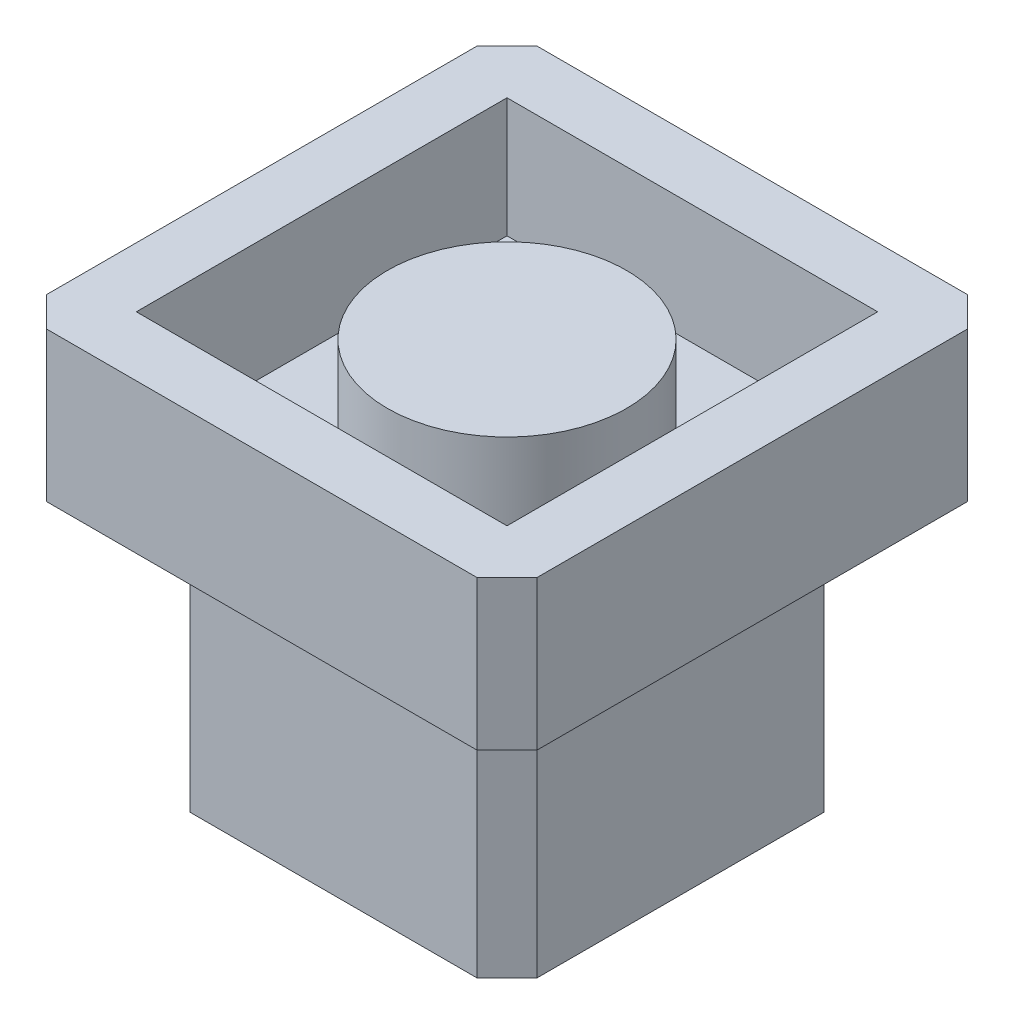
SolidWorks part; units mm, degrees
ref_plane "Front Plane" through (0, 0, 0) normal (0, 0, 1) x (1, 0, 0)
ref_plane "Top Plane" through (0, 0, 0) normal (0, 1, 0) x (1, 0, 0)
ref_plane "Right Plane" through (0, 0, 0) normal (1, 0, 0) x (0, 0, -1)
sketch "Sketch1" plane through (0, 0, 0) normal (0, 1, 0) x (1, 0, 0)
  line L0 (-4.1, 4.1) -> (-4.1, -4.1)
  line L1 (-3.1, 3.1) -> (3.1, 3.1)
  line L2 (-3.1, 3.1) -> (-3.1, -3.1)
  line L3 (-3.1, -3.1) -> (3.1, -3.1)
  line L4 (3.1, 3.1) -> (3.1, -3.1)
  line L5 (-3.1, 3.1) -> (3.1, -3.1) construction
  line L6 (-3.1, -3.1) -> (3.1, 3.1) construction
  line L7 (-4.1, -4.1) -> (4.1, -4.1)
  line L8 (4.1, 4.1) -> (4.1, -4.1)
  line L9 (-4.1, 4.1) -> (4.1, 4.1)
  circle A1 centre (0, 0) radius 2
  dimension "D1" = 4
  dimension "D2" = 6.2
  dimension "D3" = 1
extrude "Boss-Extrude1" add sketch "Sketch1" along normal blind 1.6 contours A1 region at (0, 0, 0)
extrude "Boss-Extrude2" add sketch "Sketch1<3>" along normal blind 2 separate body contours L9 L0 L7 L8 L1 L4 L3 L2 region at (0, 0, -3.984)
sketch "Sketch1<3>" plane through (0, 0, 0) normal (0, 1, 0) x (1, 0, 0) same geometry as "Sketch1"
extrude "Boss-Extrude3" add sketch "Sketch1<4>" against normal blind 0.5 contours L9 L0 L7 L8 L1 L4 L3 L2 | L4 L1 L2 L3 A1 | A1 region at (0, 0, -3.984) region at (0, 0, -3.0123) region at (0, 0, 0)
sketch "Sketch1<4>" plane through (0, 0, 0) normal (0, 1, 0) x (1, 0, 0) same geometry as "Sketch1"
sketch "Sketch3" plane through (0, -0.5, 0) normal (0, -1, 0) x (1, 0, 0)
  line L1 (-2.9, 2.9) -> (2.9, 2.9)
  line L2 (-2.9, 2.9) -> (-2.9, -2.9)
  line L3 (-2.9, -2.9) -> (2.9, -2.9)
  line L4 (2.9, 2.9) -> (2.9, -2.9)
  line L5 (-2.9, 2.9) -> (2.9, -2.9) construction
  line L6 (-2.9, -2.9) -> (2.9, 2.9) construction
  point P0 (0, 0)
  dimension "D1" = 5.8
  dimension "D2" = 5.8
extrude "Boss-Extrude4" add sketch "Sketch3" along normal blind 4.5
chamfer "Chamfer1" distance 0.5 angle 45 8 edges at (-4.1, 0.75, -4.1) (4.1, 0.75, -4.1) (-4.1, 0.75, 4.1) (4.1, 0.75, 4.1) (-2.9, -2.75, 2.9) (2.9, -2.75, 2.9) (-2.9, -2.75, -2.9) (2.9, -2.75, -2.9)
sketch "Sketch4" plane through (0, -5, 0) normal (0, -1, 0) x (1, 0, 0)
  text T1 "B\r\n"
extrude "Cut-Extrude1" cut sketch "Sketch4" against normal blind 0.2
